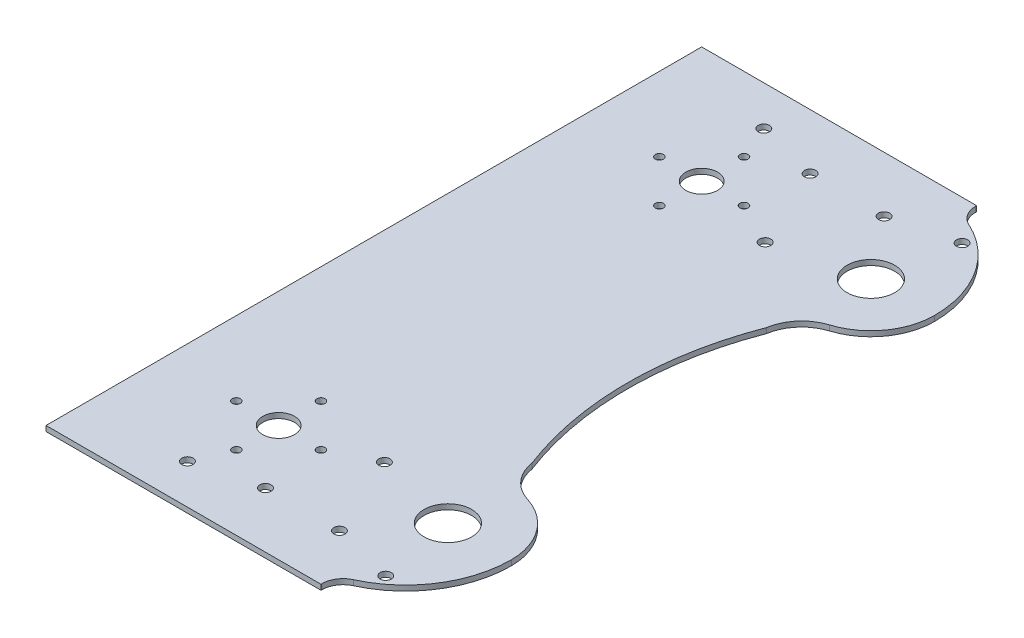
SolidWorks part; units mm, degrees
material "6061-T6 (SS)"
ref_plane "Front Plane" through (0, 0, 0) normal (0, 0, 1) x (1, 0, 0)
ref_plane "Top Plane" through (0, 0, 0) normal (0, 1, 0) x (1, 0, 0)
ref_plane "Right Plane" through (0, 0, 0) normal (1, 0, 0) x (0, 0, -1)
sketch "Sketch1" plane through (0, 0, 0) normal (0, 1, 0) x (1, 0, 0)
  line L1 (82.55, -196.85) -> (-82.55, -196.85)
  line L2 (82.55, -196.85) -> (82.55, 196.85)
  line L3 (82.55, 196.85) -> (-82.55, 196.85)
  line L4 (-82.55, -196.85) -> (-82.55, 196.85)
  line L5 (82.55, -196.85) -> (-82.55, 196.85) construction
  line L6 (82.55, 196.85) -> (-82.55, -196.85) construction
  point P0 (0, 0)
  dimension "D1" = 165.1
  dimension "D2" = 393.7
extrude "Boss-Extrude1" add sketch "Sketch1" along normal blind 3.175
sketch "Sketch3" plane through (0, 3.175, 0) normal (0, 1, 0) x (1, 0, 0)
  arc A0 (-3.175, -127) -> (-22.225, -127) centre (-12.7, -127) ccw construction
  arc A1 (-22.225, -127) -> (-3.175, -127) centre (-12.7, -127) ccw construction
  arc A2 (-3.175, -127) -> (-22.225, -127) centre (-12.7, -127) ccw
  arc A3 (-22.225, -127) -> (-3.175, -127) centre (-12.7, -127) ccw
  arc A4 (-3.175, 127) -> (-22.225, 127) centre (-12.7, 127) ccw construction
  arc A5 (-22.225, 127) -> (-3.175, 127) centre (-12.7, 127) ccw construction
  arc A6 (-3.175, 127) -> (-22.225, 127) centre (-12.7, 127) ccw
  arc A7 (-22.225, 127) -> (-3.175, 127) centre (-12.7, 127) ccw
extrude "Cut-Extrude2" cut sketch "Sketch3" against normal through all
hole_wizard "#10 (0.1935) Diameter Hole1" positions "Sketch4" profile "Sketch5" hole size "#10" standard "ANSI Inch" end condition through all
sketch "Sketch4" plane through (0, 3.175, 0) normal (0, 1, 0) x (1, 0, 0)
  arc A0 (-10.6807, -101.6) -> (-14.7193, -101.6) centre (-12.7, -101.6) ccw construction
  arc A1 (-14.7193, -101.6) -> (-10.6807, -101.6) centre (-12.7, -101.6) ccw construction
  arc A2 (-36.0807, -127) -> (-40.1193, -127) centre (-38.1, -127) ccw construction
  arc A3 (-40.1193, -127) -> (-36.0807, -127) centre (-38.1, -127) ccw construction
  arc A4 (-10.6807, -152.4) -> (-14.7193, -152.4) centre (-12.7, -152.4) ccw construction
  arc A5 (-14.7193, -152.4) -> (-10.6807, -152.4) centre (-12.7, -152.4) ccw construction
  arc A6 (14.7193, -127) -> (10.6807, -127) centre (12.7, -127) ccw construction
  arc A7 (10.6807, -127) -> (14.7193, -127) centre (12.7, -127) ccw construction
  arc A8 (-10.6807, -101.6) -> (-14.7193, -101.6) centre (-12.7, -101.6) ccw construction
  arc A9 (-14.7193, -101.6) -> (-10.6807, -101.6) centre (-12.7, -101.6) ccw construction
  arc A10 (-36.0807, -127) -> (-40.1193, -127) centre (-38.1, -127) ccw construction
  arc A11 (-40.1193, -127) -> (-36.0807, -127) centre (-38.1, -127) ccw construction
  arc A12 (-10.6807, -152.4) -> (-14.7193, -152.4) centre (-12.7, -152.4) ccw construction
  arc A13 (-14.7193, -152.4) -> (-10.6807, -152.4) centre (-12.7, -152.4) ccw construction
  arc A14 (14.7193, -127) -> (10.6807, -127) centre (12.7, -127) ccw construction
  arc A15 (10.6807, -127) -> (14.7193, -127) centre (12.7, -127) ccw construction
  arc A16 (14.7193, 127) -> (10.6807, 127) centre (12.7, 127) ccw construction
  arc A17 (10.6807, 127) -> (14.7193, 127) centre (12.7, 127) ccw construction
  arc A18 (-10.6807, 152.4) -> (-14.7193, 152.4) centre (-12.7, 152.4) ccw construction
  arc A19 (-14.7193, 152.4) -> (-10.6807, 152.4) centre (-12.7, 152.4) ccw construction
  arc A20 (-36.0807, 127) -> (-40.1193, 127) centre (-38.1, 127) ccw construction
  arc A21 (-40.1193, 127) -> (-36.0807, 127) centre (-38.1, 127) ccw construction
  arc A22 (-10.6807, 101.6) -> (-14.7193, 101.6) centre (-12.7, 101.6) ccw construction
  arc A23 (-14.7193, 101.6) -> (-10.6807, 101.6) centre (-12.7, 101.6) ccw construction
  arc A24 (14.7193, 127) -> (10.6807, 127) centre (12.7, 127) ccw
  arc A25 (10.6807, 127) -> (14.7193, 127) centre (12.7, 127) ccw
  arc A26 (-10.6807, 152.4) -> (-14.7193, 152.4) centre (-12.7, 152.4) ccw
  arc A27 (-14.7193, 152.4) -> (-10.6807, 152.4) centre (-12.7, 152.4) ccw
  arc A28 (-36.0807, 127) -> (-40.1193, 127) centre (-38.1, 127) ccw
  arc A29 (-40.1193, 127) -> (-36.0807, 127) centre (-38.1, 127) ccw
  arc A30 (-10.6807, 101.6) -> (-14.7193, 101.6) centre (-12.7, 101.6) ccw
  arc A31 (-14.7193, 101.6) -> (-10.6807, 101.6) centre (-12.7, 101.6) ccw
  point P0 (-12.7, -152.4)
  point P2 (-38.1, -127)
  point P4 (-12.7, -101.6)
  point P6 (12.7, -127)
  point P44 (-12.7, 152.4)
  point P50 (-38.1, 127)
  point P56 (-12.7, 101.6)
  point P68 (12.7, 127)
sketch "Sketch5" plane through (-12.7, 3.175, 152.4) normal (1, 0, 0) x (0, 0, 1)
  line L0 (0, 0) -> (0, 3.175)
  line L1 (0, 3.175) -> (2.4574, 3.175)
  line L2 (2.4574, 3.175) -> (2.4574, 0)
  line L5 (2.4574, 0) -> (0, 0)
  line L11 (0, -6.35) -> (0, 107.95) construction
  dimension "Thru Hole Dia." = 4.9149
  dimension "Thru Hole Depth" = 3.175
sketch "Sketch6" plane through (0, 3.175, 0) normal (0, 1, 0) x (1, 0, 0)
  line L0 (-12.7, -88.9) -> (-12.7, 88.9) construction
  line L1 (88.9, -127) -> (-12.7, -127) construction
  line L2 (88.9, 127) -> (-12.7, 127) construction
  line L3 (88.9, 127) -> (82.55, 127) construction
  line L4 (82.55, -196.85) -> (82.55, 196.85) construction
  circle A0 centre (-12.7, -127) radius 38.1 construction
  circle A1 centre (-12.7, 127) radius 38.1 construction
  circle A2 centre (88.9, -127) radius 38.1 construction
  circle A3 centre (88.9, 127) radius 38.1 construction
  dimension "D1" = 76.2
  dimension "D2" = 254
  dimension "D3" = 101.6
  dimension "D4" = 6.35
  dimension "D5" = 177.8
sketch "Sketch9" plane through (0, 0, 0) normal (0, 1, 0) x (1, 0, 0)
  line L0 (82.55, 196.85) -> (82.55, 187.5751)
  line L1 (82.55, -196.85) -> (82.55, 196.85) construction
  line L2 (82.55, 66.4249) -> (82.55, 57.15)
  line L3 (82.55, 196.85) -> (80.9625, 196.85)
  line L4 (82.55, 196.85) -> (-82.55, 196.85) construction
  line L5 (80.9625, 196.85) -> (80.9625, 57.15)
  line L6 (80.9625, 57.15) -> (82.55, 57.15)
  line L7 (0, 0) -> (145.4468, 0) construction
  line L8 (80.9625, -196.85) -> (80.9625, -57.15)
  line L9 (80.9625, -57.15) -> (82.55, -57.15)
  line L10 (82.55, -57.15) -> (82.55, -66.4249)
  line L11 (82.55, -187.5751) -> (82.55, -196.85)
  line L12 (82.55, -196.85) -> (80.9625, -196.85)
  line L13 (-82.55, -196.85) -> (82.55, -196.85) construction
  arc A0 (100.33, 90.6549) -> (127, 127) centre (88.9, 127) ccw
  arc A1 (100.33, 90.6549) -> (82.55, 66.4249) centre (107.95, 66.4249) ccw
  arc A3 (127, -127) -> (100.33, -90.6549) centre (88.9, -127) ccw
  arc A5 (82.55, -66.4249) -> (100.33, -90.6549) centre (107.95, -66.4249) ccw
  circle A6 centre (88.9, 127) radius 38.1 construction
  arc A8 (127, -127) -> (82.55, -187.5751) centre (63.5, -127) cw
  arc A10 (127, 127) -> (82.55, 187.5751) centre (63.5, 127) ccw
  point P15 (82.55, 89.4329)
  dimension "D1" = 25.4
  dimension "D4" = 139.7
  dimension "D5" = 38.1
  dimension "D2" = 25.4
  dimension "D3" = 1.5875
extrude "Boss-Extrude2" add sketch "Sketch9" along normal blind 3.175
fillet "Fillet1" radius 12.7 2 edges at (82.55, 1.5875, 187.5751) (82.55, 1.5875, -187.5751)
sketch "Sketch7" plane through (0, 3.175, 0) normal (0, 1, 0) x (1, 0, 0)
  circle A0 centre (88.9, -127) radius 14.2875
  circle A1 centre (88.9, 127) radius 14.2875
  dimension "D1" = 28.575
extrude "Cut-Extrude3" cut sketch "Sketch7" against normal through all
sketch "Sketch8" plane through (0, 3.175, 0) normal (0, 1, 0) x (1, 0, 0)
  line L0 (87.4719, 81.4517) -> (87.4719, -81.4517)
  arc A1 (87.4719, 81.4517) -> (87.4719, -81.4517) centre (266.68, 0) ccw
  arc A4 (82.55, -66.4249) -> (100.33, -90.6549) centre (107.95, -66.4249) ccw construction
  arc A5 (100.33, 90.6549) -> (82.55, 66.4249) centre (107.95, 66.4249) ccw construction
  dimension "D1" = 196.85
extrude "Cut-Extrude4" cut sketch "Sketch8" against normal through all
sketch "Sketch10" plane through (0, 3.175, 0) normal (0, 1, 0) x (1, 0, 0)
  circle A0 centre (38.1, -114.3) radius 3.3782 construction
  circle A1 centre (-21.4312, -173.0375) radius 3.3782 construction
  circle A2 centre (15.875, -163.5125) radius 3.3782 construction
  circle A3 centre (60.325, -163.5125) radius 3.3782 construction
  circle A4 centre (97.6313, -173.0375) radius 3.3782 construction
  circle A5 centre (38.1, -114.3) radius 3.3782
  circle A6 centre (-21.4312, -173.0375) radius 3.3782
  circle A7 centre (15.875, -163.5125) radius 3.3782
  circle A8 centre (60.325, -163.5125) radius 3.3782
  circle A9 centre (97.6313, -173.0375) radius 3.3782
  circle A10 centre (97.6313, 173.0375) radius 3.3782 construction
  circle A11 centre (60.325, 163.5125) radius 3.3782 construction
  circle A12 centre (15.875, 163.5125) radius 3.3782 construction
  circle A13 centre (38.1, 114.3) radius 3.3782 construction
  circle A14 centre (-21.4312, 173.0375) radius 3.3782 construction
  circle A15 centre (97.6313, 173.0375) radius 3.3782
  circle A16 centre (60.325, 163.5125) radius 3.3782
  circle A17 centre (15.875, 163.5125) radius 3.3782
  circle A18 centre (38.1, 114.3) radius 3.3782
  circle A19 centre (-21.4312, 173.0375) radius 3.3782
extrude "Cut-Extrude5" cut sketch "Sketch10" against normal through all
